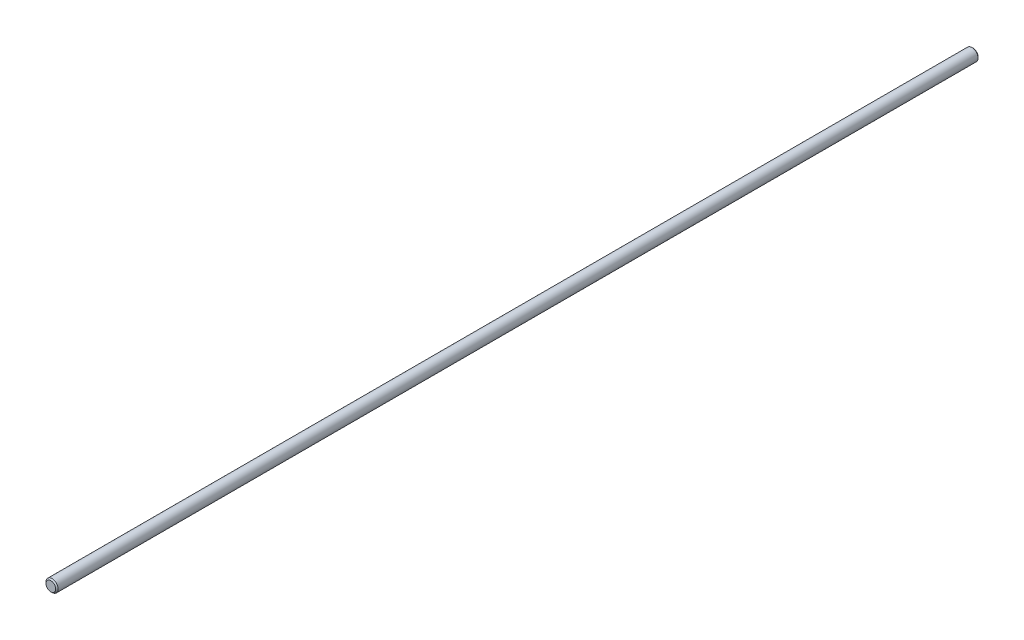
SolidWorks part; units mm, degrees
material "AISI 303 Stainless"
ref_plane "Front" through (0, 0, 0) normal (0, 0, 1) x (1, 0, 0)
ref_plane "Top" through (0, 0, 0) normal (0, 1, 0) x (1, 0, 0)
ref_plane "Right" through (0, 0, 0) normal (1, 0, 0) x (0, 0, -1)
sketch "Sketch1" plane through (0, 0, 0) normal (0, 0, 1) x (1, 0, 0)
  circle A0 centre (0, 0) radius 3.175
  dimension "dia" = 6.35
sketch "Sketch3" plane through (0, 0, 0) normal (0, 0, 1) x (1, 0, 0)
  circle A0 centre (0, 0) radius 3.175 construction
  circle A1 centre (0, 0) radius 3.175
extrude "Boss-Extrude1" add sketch "Sketch3" along normal mid plane 482.6
sketch "Sketch2" plane through (0, 0, 0) normal (1, 0, 0) x (0, 0, -1)
  line L0 (241.3, 3.175) -> (-241.3, 3.175) construction
  point P0 (-241.3, 3.175)
  point P1 (241.3, 3.175)
  point P2 (-228.6, 3.175)
  point P3 (228.6, 3.175)
  dimension "D1" = 12.7
  dimension "D2" = 12.7
chamfer "Chamfer1" distance 0.635 angle 45 2 edges at (3.175, 0, 241.3) (3.175, 0, -241.3)
equation "\"D1@Chamfer1\" = \"dia@Sketch1\" / 10"
equation "\"D1@Sketch2\"= \"dia@Sketch1\" * 2"
equation "\"D2@Sketch2\"=\"D1@Sketch2\""
